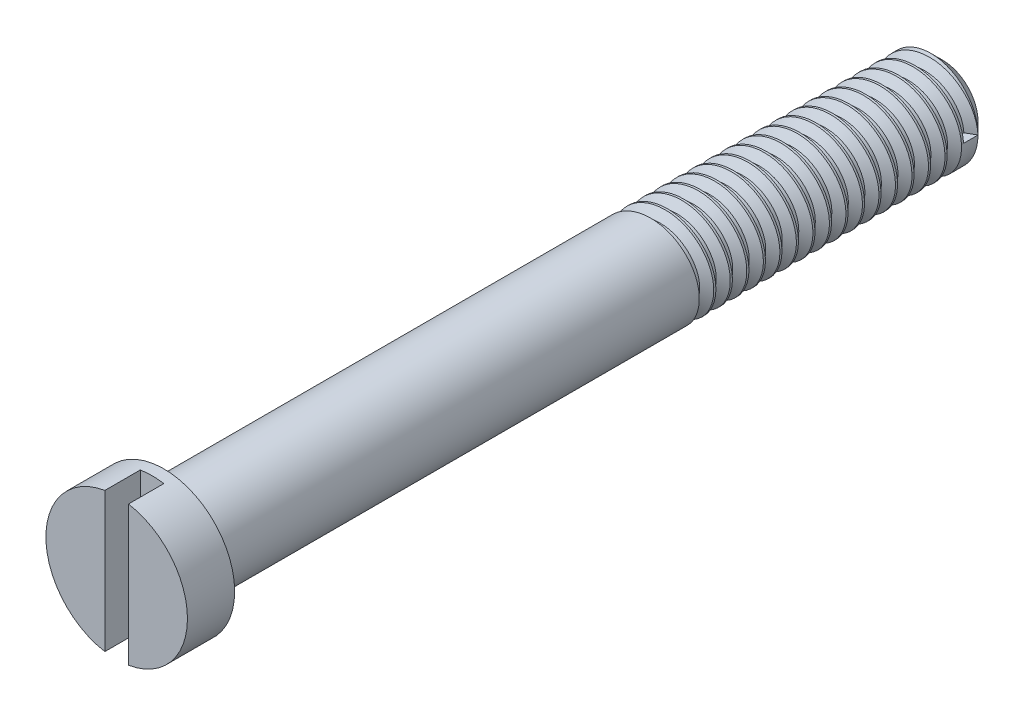
SolidWorks part; units mm, degrees
ref_plane "Front Plane" through (0, 0, 0) normal (0, 0, 1) x (1, 0, 0)
ref_plane "Top Plane" through (0, 0, 0) normal (0, 1, 0) x (1, 0, 0)
ref_plane "Right Plane" through (0, 0, 0) normal (1, 0, 0) x (0, 0, -1)
sketch "Sketch1" plane through (0, 0, 0) normal (1, 0, 0) x (0, 0, -1)
  line L1 (0, 0) -> (2, 0)
  line L2 (0, 0) -> (0, 3)
  line L3 (0, 3) -> (2, 3)
  line L4 (2, 0) -> (2, 3)
  line L5 (0, 0) -> (2, 3) construction
  line L6 (0, 3) -> (2, 0) construction
  line L7 (2, 0) -> (35, 0)
  line L8 (2, 0) -> (2, 2)
  line L9 (2, 2) -> (35, 2)
  line L10 (35, 0) -> (35, 2)
  line L11 (2, 0) -> (35, 2) construction
  line L12 (2, 2) -> (35, 0) construction
  point P4 (1, 1.5)
  point P9 (18.5, 1)
  dimension "D1" = 2
  dimension "D2" = 3
  dimension "D3" = 33
  dimension "D4" = 2
revolve "Revolve2" add sketch "Sketch1" angle 360 about L7 region at (0, 1.5, -1) region at (0, 1, -18.5)
chamfer "Chamfer1" distance 0.5 angle 45 1 edges at (2, 0, -35)
thread "Thread5" pitch 0.7 method cut profile "Thread Profile5" start angle 0, offset 0, length 11.5, pitch 0.7, diameter 4
ref_plane "Plane5" through (2, 0, -34.5) normal (0, -1, 0) x (1, 0, 0)
sketch "Thread Profile5" plane through (2, 0, -34.5) normal (0, -1, 0) x (1, 0, 0)
  line L0 (0, 0) -> (0, 0.7) construction
  line L11 (0, 0) -> (0, 0.6125)
  line L12 (0, 0.6125) -> (-0.3789, 0.3937)
  line L13 (-0.3789, 0.3937) -> (-0.3789, 0.2187)
  line L15 (-0.3789, 0.2187) -> (0, 0)
  line L17 (-0.3789, 0.3062) -> (0, 0.3062) construction
  point P2 (0, 0)
  dimension "Pitch" = 0.7
  dimension "Profile_Angle" = 60
  dimension "Profile_Land" = 0.175
  dimension "Profile_Height" = 0.3789
sketch "Sketch13" plane through (0, 0, 0) normal (0, 0, 1) x (1, 0, 0)
  line L1 (0.5, -3.0145) -> (-0.5, -3.0145)
  line L2 (0.5, -3.0145) -> (0.5, 3.0145)
  line L3 (0.5, 3.0145) -> (-0.5, 3.0145)
  line L4 (-0.5, -3.0145) -> (-0.5, 3.0145)
  line L5 (0.5, -3.0145) -> (-0.5, 3.0145) construction
  line L6 (0.5, 3.0145) -> (-0.5, -3.0145) construction
  point P0 (0, 0)
  dimension "D1" = 1
extrude "Cut-Extrude1" cut sketch "Sketch13" against normal blind 1.5
